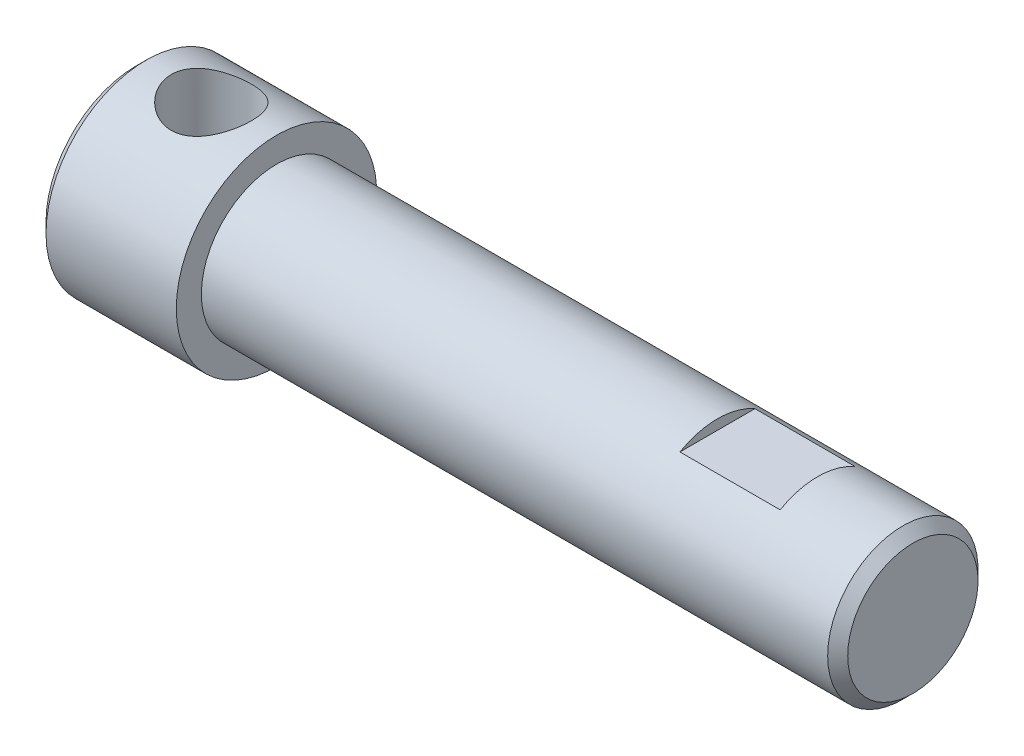
SolidWorks part; units mm, degrees
ref_plane "Plan de face" through (0, 0, 0) normal (0, 0, 1) x (1, 0, 0)
ref_plane "Plan de dessus" through (0, 0, 0) normal (0, 1, 0) x (1, 0, 0)
ref_plane "Plan de droite" through (0, 0, 0) normal (1, 0, 0) x (0, 0, -1)
sketch "Esquisse1" plane through (0, 0, 0) normal (0, 0, 1) x (1, 0, 0)
  line L3 (-18.5, 7.5) -> (44, 7.5)
  line L8 (-32.4998, 9.0002) -> (-31.5, 10)
  line L9 (-31.5, 10) -> (-18.5, 10)
  line L10 (-18.5, 10) -> (-18.5, 7.5)
  line L13 (45, 6.5) -> (44, 7.5)
  line L14 (-32.4998, 4.0002) -> (-15.4998, 4.0002)
  line L15 (-1000, 0) -> (49000, 0) construction
  line L18 (-13.1903, 0) -> (-15.4998, 4.0002)
  line L19 (-13.1903, 0) -> (45, 0)
  line L20 (-32.4998, 4.0002) -> (-32.4998, 9.0002)
  line L21 (45, 0) -> (45, 6.5)
  line L22 (44, 7.5) -> (44, 0) construction
  point P0 (0, 0)
  point P2 (-15.6472, 7.5)
  dimension "D1" = 62.5
  dimension "D2" = 135
  dimension "D3" = 13
  dimension "D4" = 2.5
  dimension "D5" = 4.619
  dimension "D6" = 7.5
  dimension "D7" = 6.5
  dimension "D8" = 135
  dimension "D9" = 1.414
  dimension "D10" = 45
  dimension "D12" = 17
  dimension "D13" = 5
revolve "Révolution5" add sketch "Esquisse1" angle 360 about L15
sketch "Esquisse5" plane through (0, 0, 0) normal (0, 0, 1) x (1, 0, 0)
  line L0 (-29, 10) -> (-29, 3)
  line L1 (-18.5, 10) -> (-31.5, 10) construction
  line L2 (-29, 3) -> (-27.75, 1.75)
  line L3 (-27.75, 1.75) -> (-25, 1.75)
  line L4 (-25, 1.75) -> (-25, 10)
  line L5 (-25, 10) -> (-29, 10)
  line L6 (-29, 3) -> (-25, 3) construction
  point P4 (-27.75, 1.9562)
  dimension "D1" = 2.75
  dimension "D2" = 4
  dimension "D3" = 135
  dimension "D4" = 2.5
  dimension "D5" = 7
revolve "Enlèvement de matière-Révolution1" cut sketch "Esquisse5" angle 360 about L4
sketch "Esquisse6" plane through (0, 0, 0) normal (0, 0, 1) x (1, 0, 0)
  line L0 (44, 7.5) -> (35.5, 7.5) construction
  line L1 (44, 7.5) -> (-18.5, 7.5) construction
  line L2 (35.5, 7.5) -> (35.5, 6.5)
  line L3 (35.5, 6.5) -> (25.5, 6.5)
  line L4 (25.5, 6.5) -> (25.5, 7.5)
  line L5 (25.5, 7.5) -> (35.5, 7.5)
  dimension "D1" = 8.5
  dimension "D2" = 1
  dimension "D3" = 10
extrude "Enlèv. mat.-Extru.3" cut sketch "Esquisse6" against normal blind 4 and the other way blind 4
